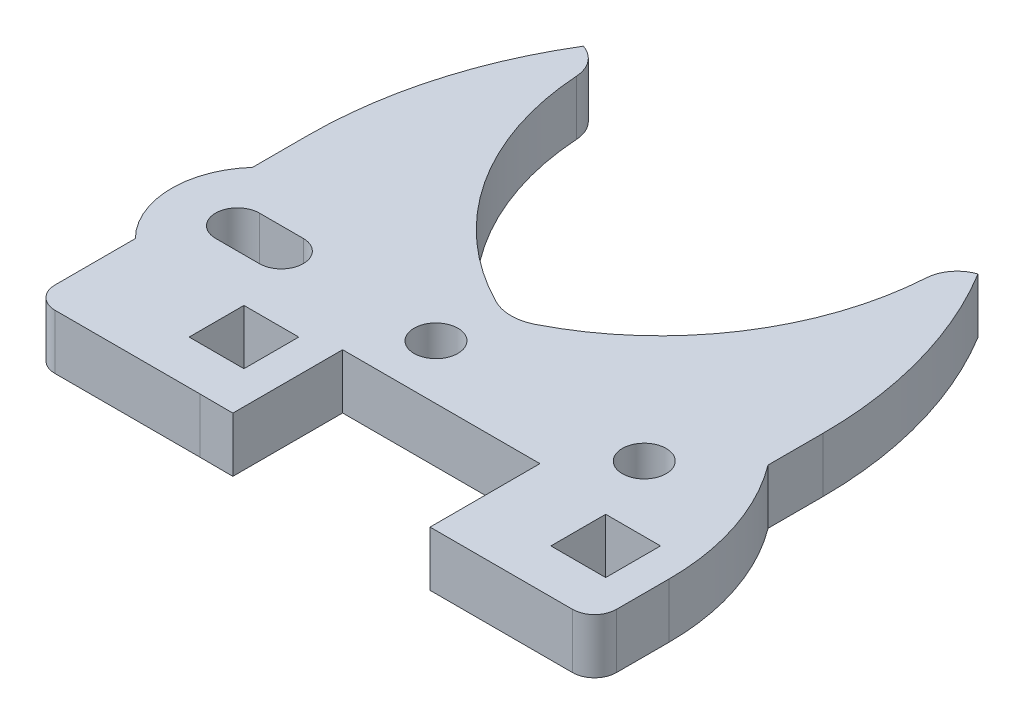
SolidWorks part; units mm, degrees
ref_plane "Front Plane" through (0, 0, 0) normal (0, 0, 1) x (1, 0, 0)
ref_plane "Top Plane" through (0, 0, 0) normal (0, 1, 0) x (1, 0, 0)
ref_plane "Right Plane" through (0, 0, 0) normal (1, 0, 0) x (0, 0, -1)
sketch "Sketch1" plane through (0, 0, 0) normal (0, 1, 0) x (1, 0, 0)
  line L0 (0, 29.8237) -> (0, 15.6254) construction
  line L1 (16, 33.9437) -> (16, 32.9437)
  line L2 (-13, -11.0182) -> (-21.2332, -11.0182)
  line L3 (13, -1.0182) -> (-2.9987, -1.0182)
  line L4 (0, -10.8496) -> (0, -28.2979) construction
  line L5 (-19.5894, 5.9818) -> (-15.5894, 5.9818)
  line L6 (-19.5894, 1.9818) -> (-15.5894, 1.9818)
  line L7 (-7.9987, -11.0182) -> (-7.9987, -11.0403)
  line L8 (-16, 33.9437) -> (-16, 32.9437)
  line L9 (13, -11.0403) -> (26, -11.0403)
  line L10 (13, -11.0403) -> (13, -1.0182)
  line L11 (28, -9.0403) -> (28, -4.239)
  line L12 (-23.2332, -9.0182) -> (-23.2332, -1.6918)
  line L13 (-7.9987, -11.0182) -> (-4.9987, -11.0314)
  line L14 (16, 33.9437) -> (18, 33.9437)
  line L15 (23.5148, 9.2804) -> (23.5148, 14.2804)
  line L16 (-13, -11.0182) -> (-7.9987, -11.0182)
  line L17 (-23.5148, 9.2804) -> (-23.5148, 14.2804)
  line L18 (20, -7.0182) -> (25, -7.0182)
  line L19 (20, -7.0182) -> (20, -2.0182)
  line L20 (-13, -7.0182) -> (-7.9987, -7.0182)
  line L21 (20, -2.0182) -> (25, -2.0182)
  line L22 (-16, 33.9437) -> (-18, 33.9437)
  line L25 (-13, -7.0182) -> (-13, -2.0182)
  line L27 (-13, -2.0182) -> (-7.9987, -2.0182)
  line L28 (-7.9987, -7.0182) -> (-7.9987, -2.0182)
  line L29 (-7.9987, -11.0182) -> (-13, -11.0182)
  line L30 (-2.9987, -1.0182) -> (-4.9987, -1.0182)
  line L31 (-4.9987, -11.0403) -> (-4.9987, -1.0182)
  line L32 (25, -7.0182) -> (25, -2.0182)
  arc A0 (26, -11.0403) -> (28, -9.0403) centre (26, -9.0403) ccw
  arc A1 (23.5148, 14.2804) -> (18, 33.9437) centre (-14.2977, 14.2804) ccw
  arc A2 (28, -4.239) -> (23.5148, 9.2804) centre (5.3821, -4.239) ccw
  arc A3 (-23.5148, 14.2804) -> (-18, 33.9437) centre (14.2977, 14.2804) cw
  circle A4 centre (17.555, 3.9437) radius 2
  arc A5 (16, 32.9437) -> (0, 8.9437) centre (-10, 32.9437) cw
  arc A6 (-16, 32.9437) -> (0, 8.9437) centre (10, 32.9437) ccw
  circle A7 centre (-1.445, 3.9437) radius 2
  arc A8 (-19.5894, 5.9818) -> (-19.5894, 1.9818) centre (-19.5894, 3.9818) ccw
  arc A9 (-15.5894, 1.9818) -> (-15.5894, 5.9818) centre (-15.5894, 3.9818) ccw
  arc A10 (-21.2332, -11.0182) -> (-23.2332, -9.0182) centre (-21.2332, -9.0182) cw
  arc A12 (-23.2332, -1.6918) -> (-23.5148, 9.2804) centre (-17.555, 3.9437) cw
  point P5 (0, 3.9437)
  point P24 (-17.555, 3.9437)
  dimension "D1" = 2
  dimension "D3" = 2
  dimension "D2" = 19
  dimension "D4" = 32
  dimension "D5" = 36
extrude "Boss-Extrude1" add sketch "Sketch1" along normal blind 5 contours A12 L29 L3 A4 A7 A9 L6 A8 L5 region at (0.6452, 0, -7.2659)
fillet "Fillet1" radius 4 1 edges at (0, 2.5, -8.9437)
fillet "Fillet2" radius 3 1 edges at (16, 2.5, -33.9437)
fillet "Fillet3" radius 3 1 edges at (-16, 2.5, -33.9437)
